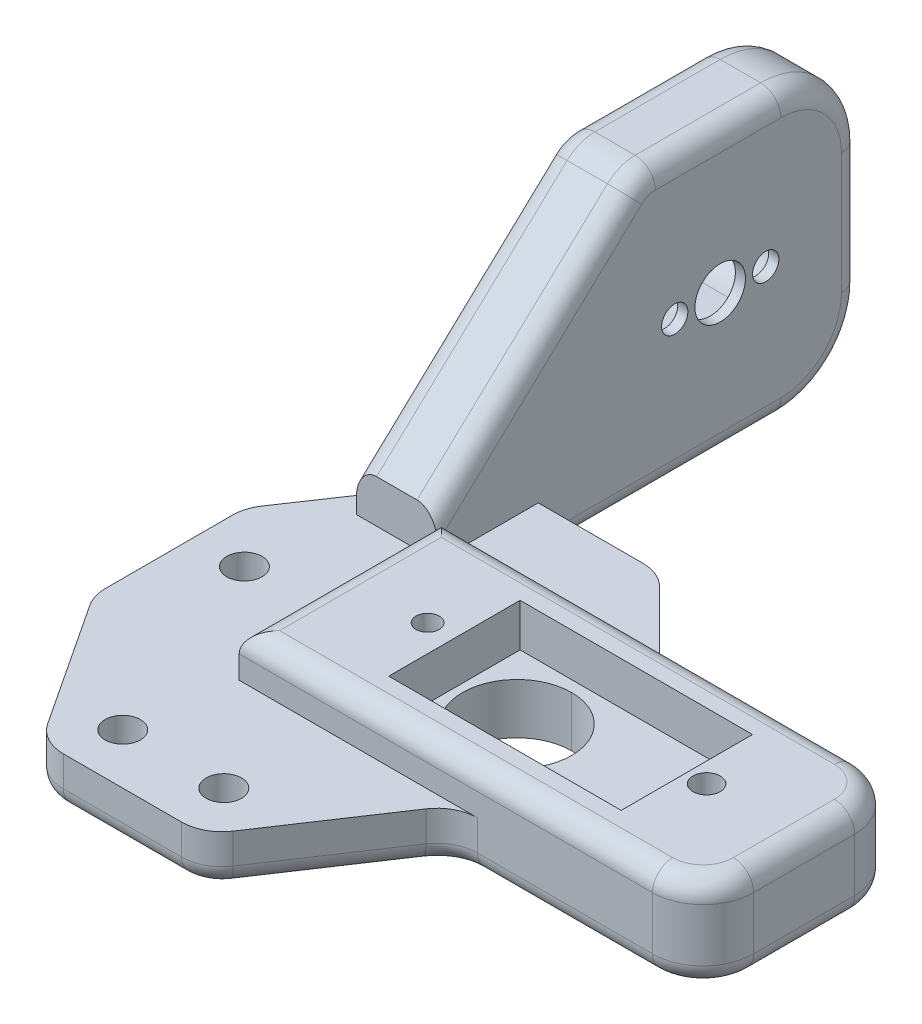
SolidWorks part; units mm, degrees
ref_plane "Front Plane" through (0, 0, 0) normal (0, 0, 1) x (1, 0, 0)
ref_plane "Top Plane" through (0, 0, 0) normal (0, 1, 0) x (1, 0, 0)
ref_plane "Right Plane" through (0, 0, 0) normal (1, 0, 0) x (0, 0, -1)
sketch "Sketch2" plane through (0, 0, 0) normal (0, 1, 0) x (1, 0, 0)
  line L0 (0, 0) -> (45, 0) construction
  line L1 (-15.0807, 5.0509) -> (-4.9985, 19.9985)
  line L2 (-4.9985, 19.9985) -> (11.0015, 19.9985)
  line L3 (11.0015, 19.9985) -> (21, 10)
  line L4 (21, 10) -> (45, 10)
  line L5 (45, 10) -> (45, -10)
  line L6 (-15.0807, 5.0509) -> (-15.0807, -9.9491)
  line L8 (20.8449, -10) -> (45, -10)
  line L9 (10.8437, -25.0019) -> (20.8449, -10)
  line L10 (-5.1563, -25.0019) -> (10.8437, -25.0019)
  line L11 (-15.0807, -9.9491) -> (-5.1563, -25.0019)
  point P11 (45, 0)
  dimension "D1" = 18.03
  dimension "D2" = 16
  dimension "D3" = 14.14
  dimension "D4" = 24
  dimension "D5" = 20
  dimension "D6" = 15
  dimension "D7" = 45
  dimension "D8" = 225
  dimension "D9" = 146
  dimension "D10" = 18.03
  dimension "D13" = 16
  dimension "D14" = 18.03
extrude "Boss-Extrude1" add sketch "Sketch2" along normal blind 5
sketch "Sketch3" plane through (0, 5, 0) normal (0, 1, 0) x (1, 0, 0)
  line L0 (45, 0) -> (-12.1274, 0) construction
  line L1 (45, -10) -> (45, 10) construction
  line L2 (-2.1179, -20.0019) -> (7.8821, -20.0019) construction
  line L4 (11.5, 5.4) -> (22.3, 5.4)
  line L5 (11.5, 5.4) -> (11.5, -5.4)
  line L6 (11.5, -5.4) -> (22.3, -5.4)
  line L7 (22.3, 5.4) -> (22.3, -5.4)
  line L8 (11.5, 5.4) -> (22.3, -5.4) construction
  line L9 (11.5, -5.4) -> (22.3, 5.4) construction
  line L10 (-5.1563, -25.0019) -> (10.8437, -25.0019) construction
  line L11 (-15.0807, -9.9491) -> (20.8449, -10) construction
  line L12 (-15.0807, 5.0509) -> (-15.0807, -9.9491) construction
  circle A0 centre (-10.0807, 0) radius 1.75
  circle A1 centre (-2.1179, -20.0019) radius 1.75
  circle A2 centre (7.8821, -20.0019) radius 1.75
  point P11 (16.9, 0)
  point P22 (2.8821, -9.9745)
  point P23 (2.8821, -20.0019)
  point P26 (-15.0807, -2.4491)
  dimension "D4" = 3.5
  dimension "D7" = 5
  dimension "D1" = 10
  dimension "D2" = 10.8
  dimension "D3" = 10.8
  dimension "D5" = 5
  dimension "D6" = 0
  dimension "D8" = 22.7
extrude "Cut-Extrude1" cut sketch "Sketch3" against normal through all
fillet "Fillet1" 2 edges at (11.5, 2.5, -5.4) (11.5, 2.5, 5.4) type full round first side face at (16.9, 2.5, -5.4) second side face at (16.9, 2.5, 5.4) middle face at (11.5, 2.5, 0)
fillet "Fillet2" 2 edges at (22.3, 2.5, -5.4) (22.3, 2.5, 5.4) type full round first side face at (19.6, 2.5, -5.4) second side face at (19.6, 2.5, 5.4) middle face at (22.3, 2.5, 0)
sketch "Sketch4" plane through (0, 5, 0) normal (0, 1, 0) x (1, 0, 0)
  line L0 (45, 10) -> (21, 10) construction
  line L1 (-0.6, 10) -> (34.4, 10)
  line L2 (-0.6, 10) -> (-0.6, -10)
  line L3 (-0.6, -10) -> (34.4, -10)
  line L4 (34.4, 10) -> (34.4, -10)
  line L5 (-0.6, 10) -> (34.4, -10) construction
  line L6 (-0.6, -10) -> (34.4, 10) construction
  line L7 (5.4, 6.5) -> (28.4, 6.5)
  line L8 (5.4, 6.5) -> (5.4, -6.5)
  line L9 (5.4, -6.5) -> (28.4, -6.5)
  line L10 (28.4, 6.5) -> (28.4, -6.5)
  line L11 (5.4, 6.5) -> (28.4, -6.5) construction
  line L12 (5.4, -6.5) -> (28.4, 6.5) construction
  arc A1 (16.9, -5.4) -> (16.9, 5.4) centre (16.9, 0) ccw construction
  dimension "D1" = 23
  dimension "D2" = 13
  dimension "D3" = 6
extrude "Boss-Extrude2" add sketch "Sketch4" along normal blind 4.25
sketch "Sketch5" plane through (0, 5, 0) normal (0, 1, 0) x (1, 0, 0)
  line L1 (34.4, 10) -> (34.4, -10)
  line L2 (34.4, 10) -> (34.4, -10)
  line L6 (34.4, -10) -> (45, -10)
  line L7 (34.4, -10) -> (45, -10)
  line L8 (45, -10) -> (45, 10)
  line L9 (45, -10) -> (45, 10)
  line L10 (45, 10) -> (34.4, 10)
  line L11 (45, 10) -> (34.4, 10)
  dimension "D1" = 0
extrude "Cut-Extrude2" cut sketch "Sketch5" against normal through all
fillet "Fillet4" radius 4 2 edges at (34.4, 4.625, 10) (34.4, 4.625, -10)
sketch "Sketch6" plane through (0, 0, -19.9985) normal (0, 0, -1) x (-1, 0, 0)
  line L0 (-11.0015, 0) -> (4.9985, 0) construction
  line L1 (0.9985, 0) -> (8.9985, 0)
  line L2 (0.9985, 0) -> (0.9985, 28)
  line L3 (0.9985, 28) -> (8.9985, 28)
  line L4 (8.9985, 0) -> (8.9985, 28)
  line L5 (4.9985, 5) -> (4.9985, 0) construction
  point P8 (4.9985, 0)
  dimension "D1" = 4
  dimension "D2" = 4
  dimension "D3" = 28
extrude "Boss-Extrude3" add sketch "Sketch6" along normal blind 32
sketch "Sketch7" plane through (-0.9985, 0, 0) normal (1, 0, 0) x (0, 0, -1)
  line L0 (33.4985, 14) -> (42.4985, 14) construction
  line L1 (51.9985, 0) -> (19.9985, 0) construction
  line L2 (51.9985, 28) -> (51.9985, 0) construction
  circle A0 centre (33.4985, 14) radius 1.3
  circle A1 centre (37.9985, 14) radius 2.5
  circle A2 centre (42.4985, 14) radius 1.3
  point P6 (37.9985, 14)
  dimension "D2" = 2.6
  dimension "D3" = 5
  dimension "D1" = 9
  dimension "D4" = 14
  dimension "D5" = 14
extrude "Cut-Extrude3" cut sketch "Sketch7" against normal blind 32
fillet "Fillet5" radius 8 2 edges at (-4.9985, 0, -51.9985) (-4.9985, 28, -51.9985)
sketch "Sketch8" plane through (-0.9985, 0, 0) normal (1, 0, 0) x (0, 0, -1)
  line L0 (10, 5) -> (10, 9.25)
  line L1 (10, 9.25) -> (19.9985, 28)
  line L2 (19.9985, 28) -> (19.9985, 5)
  line L4 (10, 5) -> (10, 0)
  line L5 (10, 0) -> (19.9985, 0)
  line L6 (19.9985, 0) -> (19.9985, 5)
extrude "Boss-Extrude4" add sketch "Sketch8" against normal up to surface (8 mm away) up to face at (-8.9985, 14, -34.7985)
sketch "Sketch9" plane through (-8.9985, 0, 0) normal (-1, 0, 0) x (0, 0, 1)
  line L1 (-44.9985, 17.5) -> (-30.9985, 17.5)
  line L2 (-44.9985, 17.5) -> (-44.9985, 10.5)
  line L3 (-44.9985, 10.5) -> (-30.9985, 10.5)
  line L4 (-30.9985, 17.5) -> (-30.9985, 10.5)
  line L5 (-44.9985, 17.5) -> (-30.9985, 10.5) construction
  line L6 (-44.9985, 10.5) -> (-30.9985, 17.5) construction
  point P0 (-37.9985, 14)
  dimension "D1" = 7
  dimension "D2" = 14
extrude "Cut-Extrude4" cut sketch "Sketch9" against normal blind 7
fillet "Fillet6" 2 edges at (-5.4985, 17.5, -44.9985) (-5.4985, 10.5, -44.9985) type full round first side face at (-5.4985, 17.5, -37.9985) second side face at (-5.4985, 10.5, -37.9985) middle face at (-5.4985, 14, -44.9985)
fillet "Fillet7" 2 edges at (-5.4985, 17.5, -30.9985) (-5.4985, 10.5, -30.9985) type full round first side face at (-5.4985, 17.5, -36.2485) second side face at (-5.4985, 10.5, -36.2485) middle face at (-5.4985, 14, -30.9985)
sketch "Sketch10" plane through (-8.9985, 0, 0) normal (-1, 0, 0) x (0, 0, 1)
  line L0 (-19.9985, 28) -> (-10, 9.25)
  line L1 (-10, 9.25) -> (-29.9985, 28)
  line L2 (-43.9985, 28) -> (-19.9985, 28) construction
  line L3 (-29.9985, 28) -> (-19.9985, 28)
  dimension "D1" = 10
extrude "Cut-Extrude5" cut sketch "Sketch10" against normal up to surface (8 mm away) up to face at (-0.9985, 15.3, -33.4985)
fillet "Fillet8" radius 4 9 edges at (11.0015, 2.5, -19.9985) (21, 2.5, -10) (20.8449, 2.5, 10) (10.8437, 2.5, 25.0019) (-5.1563, 2.5, 25.0019) (-15.0807, 2.5, 9.9491) (-15.0807, 2.5, -5.0509) (-4.9985, 28, -29.9985) (-8.9985, 2.5, -14.0682)
sketch "Sketch12" plane through (0, 9.25, 0) normal (0, 1, 0) x (1, 0, 0)
  line L0 (34.4, -6) -> (34.4, 6) construction
  line L1 (34.4, -6) -> (34.4, 6)
  line L2 (30.4, 10) -> (38.3, 10)
  line L3 (38.3, 10) -> (38.3, -10)
  line L4 (38.3, -10) -> (30.4, -10)
  arc A0 (30.4, -10) -> (34.4, -6) centre (30.4, -6) ccw construction
  arc A1 (34.4, 6) -> (30.4, 10) centre (30.4, 6) ccw construction
  arc A2 (30.4, -10) -> (34.4, -6) centre (30.4, -6) ccw
  arc A3 (34.4, 6) -> (30.4, 10) centre (30.4, 6) ccw
  dimension "D1" = 7.9
extrude "Boss-Extrude6" add sketch "Sketch12" against normal up to surface (9.25 mm away) up to face at (6.9674, 0, -2.9501)
sketch "Sketch13" plane through (0, 9.25, 0) normal (0, 1, 0) x (1, 0, 0)
  line L0 (5.4, -6.5) -> (28.4, -6.5) construction
  line L1 (5.4, 6.5) -> (10.7, 6.5)
  line L2 (5.4, 6.5) -> (5.4, -6.5)
  line L3 (5.4, -6.5) -> (10.7, -6.5)
  line L4 (10.7, 6.5) -> (10.7, -6.5)
  line L5 (5.4, 0) -> (10.7, 0) construction
  circle A0 centre (8.05, 0) radius 1.15
  point P11 (8.05, 0)
  dimension "D2" = 2.3
  dimension "D1" = 5.3
extrude "Boss-Extrude9" add sketch "Sketch13" against normal up to surface (4.25 mm away) up to face at (16.9, 5, 0)
sketch "Sketch14" plane through (0, 9.25, 0) normal (0, 1, 0) x (1, 0, 0)
  circle A0 centre (35.65, 0) radius 1.35
  circle A1 centre (8.05, 0) radius 1.15 construction
  dimension "D1" = 27.6
  dimension "D2" = 2.7
extrude "Cut-Extrude6" cut sketch "Sketch14" against normal up to surface (4.25 mm away) up to face at (8.05, 5, 1.15)
sketch "Sketch15" plane through (0, 9.25, 0) normal (0, 1, 0) x (1, 0, 0)
  line L1 (38.3, 10) -> (45.3, 10)
  line L2 (38.3, 10) -> (38.3, -10)
  line L3 (38.3, -10) -> (45.3, -10)
  line L4 (45.3, 10) -> (45.3, -10)
  point P5 (0, 0)
  dimension "D1" = 7
extrude "Boss-Extrude10" add sketch "Sketch15" against normal up to surface (9.25 mm away) up to face at (5.0282, 0, -3.2311)
fillet "Fillet11" radius 5 2 edges at (45.3, 4.625, 10) (45.3, 4.625, -10)
fillet "Fillet12" radius 2 40 edges at (-0.9985, 18.084, -19.4222) (-0.9985, 27.7197, -30.1093) (-0.9985, 28, -37.7894) (-0.9985, 25.6569, -49.6553) (-0.9985, 0, -31.9985) (-0.9985, 2.3431, -49.6553) (19.85, 9.25, 10) (43.8355, 9.25, 8.5355) (45.3, 9.25, 0) (43.8355, 9.25, -8.5355) (4.1731, 0, -19.9985) (10.8754, 0, -19.694) (16.0008, 0, -14.9992) (21.1261, 0, -10.3045) (31.4784, 0, -10) (-8.9985, 18.084, -19.4222) (-8.9985, 27.7197, -30.1093) (-8.9985, 28, -37.7894) (-8.9985, 25.6569, -49.6553) (-8.9985, 14, -51.9985) (-8.9985, 2.3431, -49.6553) (-8.9985, 0, -29.6448) (-9.1733, 0, -14.1217) (-12.0396, 0, -9.5596) (-14.906, 0, -4.9975) (-15.0807, 0, 2.4605) (-14.9121, 0, 9.8985) (-10.3811, 0, 17.0772) (-4.8989, 0, 24.5237) (2.8502, 0, 25.0019) (10.5903, 0, 24.5286) (15.8443, 0, 17.5009) (21.0982, 0, 10.4733) (31.6428, 0, 10) (43.8355, 0, 8.5355) (45.3, 0, 0) (-0.9985, 14, -51.9985) (-0.6, 9.25, 0) (19.85, 9.25, -10) (43.8355, 0, -8.5355)
sketch "Sketch16" plane through (0, 9.25, 0) normal (0, 1, 0) x (1, 0, 0)
  line L1 (28.4, 6.5) -> (33.7, 6.5)
  line L2 (28.4, 6.5) -> (28.4, -6.5)
  line L3 (28.4, -6.5) -> (33.7, -6.5)
  line L4 (33.7, 6.5) -> (33.7, -6.5)
  point P5 (0, 0)
  dimension "D1" = 5.3
extrude "Cut-Extrude7" cut sketch "Sketch16" against normal up to surface (4.25 mm away) up to face at (19.55, 5, 0)
